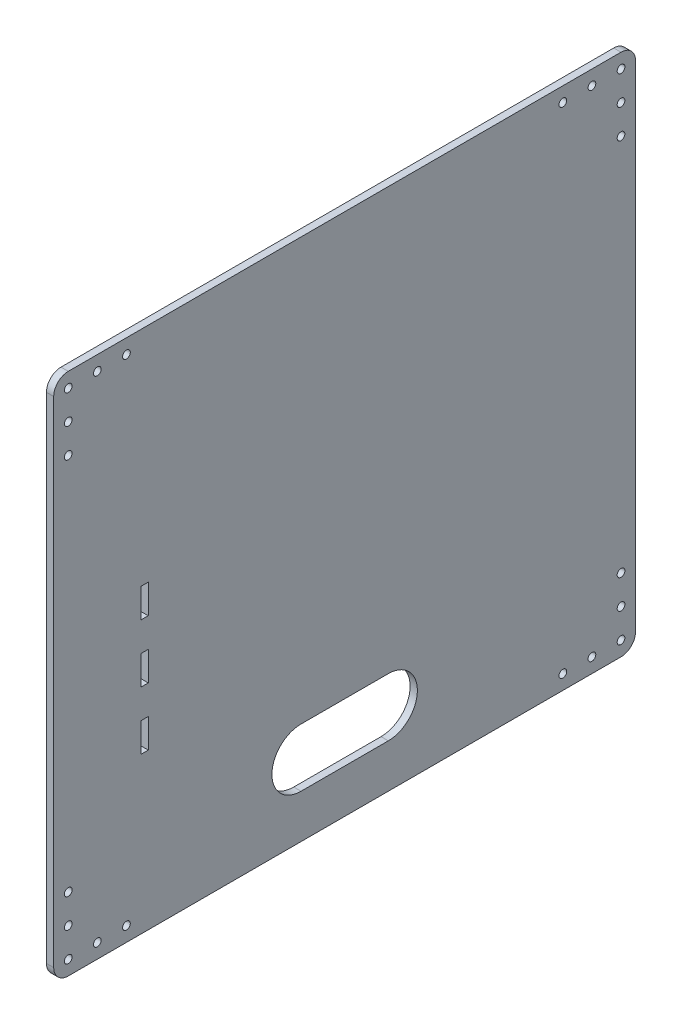
SolidWorks part; units mm, degrees
material "Acrílico (médio-alto impacto)"
ref_plane "Plano frontal" through (0, 0, 0) normal (0, 0, 1) x (1, 0, 0)
ref_plane "Plano superior" through (0, 0, 0) normal (0, 1, 0) x (1, 0, 0)
ref_plane "Plano direito" through (0, 0, 0) normal (1, 0, 0) x (0, 0, -1)
sketch "Esboço1" plane through (0, 0, 0) normal (1, 0, 0) x (0, 0, -1)
  line L1 (-200, 180) -> (200, 180)
  line L2 (-200, 180) -> (-200, -180)
  line L3 (-200, -180) -> (200, -180)
  line L4 (200, 180) -> (200, -180)
  line L5 (-200, 180) -> (200, -180) construction
  line L6 (-200, -180) -> (200, 180) construction
  point P0 (0, 0)
  dimension "D1" = 400
  dimension "D2" = 360
extrude "Ressalto-extrusão1" add sketch "Esboço1" along normal mid plane 5
fillet "Filete1" radius 10 4 edges at (0, 180, -200) (0, -180, -200) (0, -180, 200) (0, 180, 200)
sketch "Esboço2" plane through (2.5, 0, 0) normal (1, 0, 0) x (0, 0, -1)
  line L0 (-200, 170) -> (-200, -170) construction
  line L1 (-190, -180) -> (190, -180) construction
  circle A0 centre (-190, -170) radius 2.65
  circle A1 centre (-170, -170) radius 2.65
  circle A2 centre (-150, -170) radius 2.65
  circle A3 centre (-190, -150) radius 2.65
  circle A4 centre (-190, -130) radius 2.65
  dimension "D1" = 5.3
  dimension "D2" = 10
  dimension "D3" = 10
  dimension "D4" = 3
  dimension "D5" = 3
extrude "Corte-extrusão1" cut sketch "Esboço2" against normal through all
ref_axis "Eixo3" through (-3.3, 0, 0) along (1, 0, 0)
mirror "Espelhar1" about plane through (0, 0, 0) normal (0, 0, 1) of "Corte-extrusão1"
mirror "Espelhar2" about plane through (0, 0, 0) normal (0, 1, 0) of "Espelhar1"
sketch "Esboço3" plane through (2.5, 0, 0) normal (1, 0, 0) x (0, 0, -1)
  line L1 (-135, -53) -> (-140, -53)
  line L2 (-135, -53) -> (-135, -73)
  line L3 (-135, -73) -> (-140, -73)
  line L4 (-140, -53) -> (-140, -73)
  line L6 (-200, 170) -> (-200, -170) construction
  line L7 (-190, -180) -> (190, -180) construction
  dimension "D1" = 5
  dimension "D2" = 20
  dimension "D3" = 60
  dimension "D4" = 107
extrude "Corte-extrusão2" cut sketch "Esboço3" against normal through all
pattern_linear "Padrão linear1" count 3 spacing 40 along (0, 1, 0) of "Corte-extrusão2"
sketch "Esboço4" plane through (-2.5, 0, 0) normal (-1, 0, 0) x (0, 0, 1)
  line L0 (200, 0) -> (-200, 0) construction
  line L1 (200, 170) -> (200, -170) construction
  line L2 (-200, -170) -> (-200, 170) construction
  line L3 (0, -180) -> (0, 180) construction
  line L4 (190, -180) -> (-190, -180) construction
  line L5 (-190, 180) -> (190, 180) construction
  line L6 (200, -130) -> (-200, -130) construction
  line L7 (30, -130) -> (-30, -130) construction
  line L8 (30, -150) -> (-30, -150)
  line L9 (30, -110) -> (-30, -110)
  arc A0 (30, -150) -> (30, -110) centre (30, -130) ccw
  arc A1 (-30, -110) -> (-30, -150) centre (-30, -130) ccw
  point P16 (0, -130)
  dimension "D1" = 130
  dimension "D2" = 40
  dimension "D3" = 60
extrude "Corte-extrusão3" cut sketch "Esboço4" against normal through all
